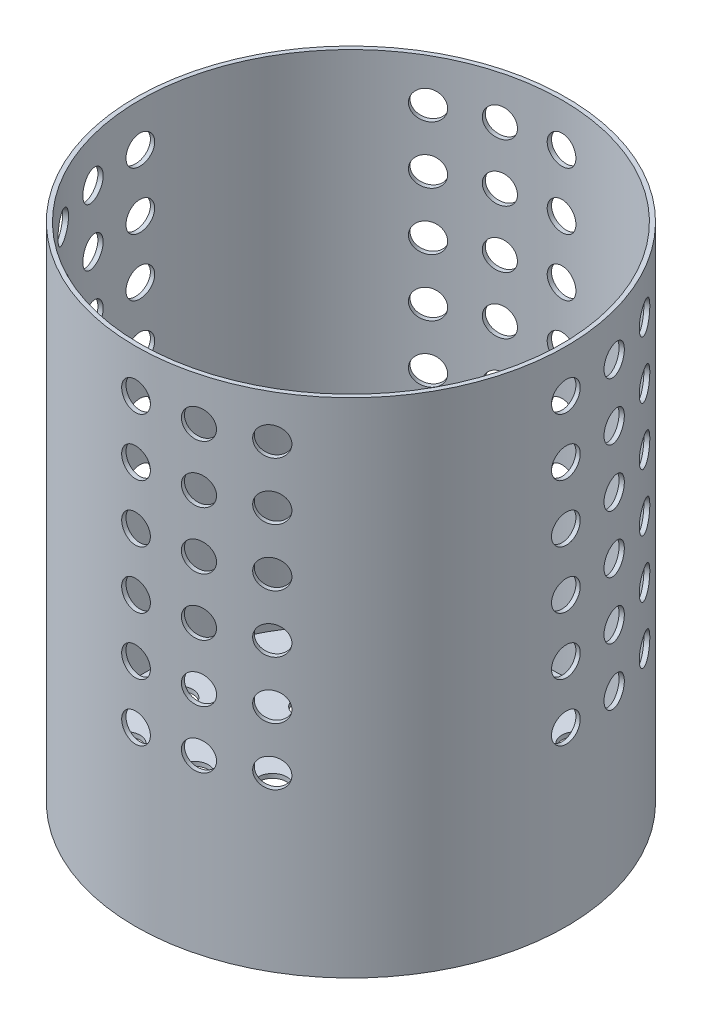
SolidWorks part; units mm, degrees
ref_plane "Front Plane" through (0, 0, 0) normal (0, 0, 1) x (1, 0, 0)
ref_plane "Top Plane" through (0, 0, 0) normal (0, 1, 0) x (1, 0, 0)
ref_plane "Right Plane" through (0, 0, 0) normal (1, 0, 0) x (0, 0, -1)
sketch "Sketch1" plane through (0, 0, 0) normal (0, 1, 0) x (1, 0, 0)
  circle A0 centre (0, 0) radius 75
  dimension "D1" = 150
extrude "Boss-Extrude1" add sketch "Sketch1" along normal blind 175
shell "Shell2" thickness 1.5 removed face at (0, 175, 75)
sketch "Sketch2" plane through (0, 0, 0) normal (0, -1, 0) x (1, 0, 0)
  circle A0 centre (0, 0) radius 5
  circle A1 centre (0, 0) radius 20 construction
  circle A2 centre (0, 0) radius 40 construction
  circle A3 centre (0, 0) radius 60 construction
  circle A4 centre (0, 20) radius 4.979
  circle A5 centre (0, 40) radius 4.979
  circle A6 centre (0, 60) radius 4.979
  circle A7 centre (17.3205, 10) radius 4.979
  circle A8 centre (17.3205, -10) radius 4.979
  circle A9 centre (0, -20) radius 4.979
  circle A10 centre (-17.3205, -10) radius 4.979
  circle A11 centre (-17.3205, 10) radius 4.979
  circle A12 centre (20, 34.641) radius 4.979
  circle A13 centre (34.641, 20) radius 4.979
  circle A14 centre (40, 0) radius 4.979
  circle A15 centre (34.641, -20) radius 4.979
  circle A16 centre (20, -34.641) radius 4.979
  circle A17 centre (0, -40) radius 4.979
  circle A18 centre (-20, -34.641) radius 4.979
  circle A19 centre (-34.641, -20) radius 4.979
  circle A20 centre (-40, 0) radius 4.979
  circle A21 centre (-34.641, 20) radius 4.979
  circle A22 centre (-20, 34.641) radius 4.979
  circle A23 centre (22.961, 55.4328) radius 4.979
  circle A24 centre (42.4264, 42.4264) radius 4.979
  circle A25 centre (55.4328, 22.961) radius 4.979
  circle A26 centre (60, 0) radius 4.979
  circle A27 centre (55.4328, -22.961) radius 4.979
  circle A28 centre (42.4264, -42.4264) radius 4.979
  circle A29 centre (22.961, -55.4328) radius 4.979
  circle A30 centre (0, -60) radius 4.979
  circle A31 centre (-22.961, -55.4328) radius 4.979
  circle A32 centre (-42.4264, -42.4264) radius 4.979
  circle A33 centre (-55.4328, -22.961) radius 4.979
  circle A34 centre (-60, 0) radius 4.979
  circle A35 centre (-55.4328, 22.961) radius 4.979
  circle A36 centre (-42.4264, 42.4264) radius 4.979
  circle A37 centre (-22.961, 55.4328) radius 4.979
  point P24 (0, 0)
  point P47 (0, 0)
  point P78 (0, 0)
  dimension "D1" = 10
  dimension "D2" = 40
  dimension "D3" = 80
  dimension "D4" = 120
  dimension "D5" = 6
  dimension "D6" = 12
  dimension "D7" = 16
extrude "Cut-Extrude1" cut sketch "Sketch2" against normal blind 175
ref_plane "Plane1" through (75, 0, 0) normal (1, 0, 0) x (0, 0, -1)
sketch "Sketch3" plane through (75, 0, 0) normal (1, 0, 0) x (0, 0, -1)
  line L0 (73.5, 175) -> (-73.5, 175) construction
  circle A0 centre (0, 160) radius 5
  circle A1 centre (0, 140) radius 5
  circle A2 centre (0, 120) radius 5
  circle A3 centre (0, 100) radius 5
  circle A4 centre (0, 80) radius 5
  circle A5 centre (0, 60) radius 5
  point P4 (0, 0)
  dimension "D2" = 10
  dimension "D1" = 15
  dimension "D3" = 6
extrude "Cut-Extrude2" cut sketch "Sketch3" against normal blind 35
pattern_circular "CirPattern1" count 3 every 15 about axis through (0, 175, 0) along (0, 1, 0) of "Cut-Extrude2"
pattern_circular "CirPattern2" count 4 every 90 about axis through (0, 175, 0) along (0, 1, 0) of "CirPattern1"
